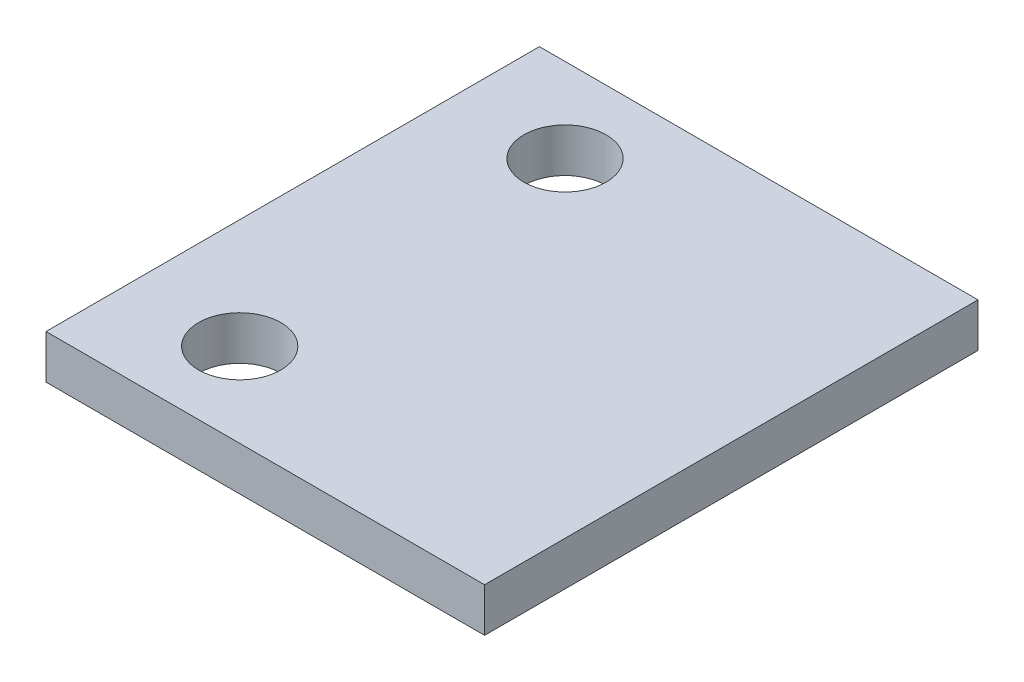
SolidWorks part; units mm, degrees
ref_plane "Front Plane" through (0, 0, 0) normal (0, 0, 1) x (1, 0, 0)
ref_plane "Top Plane" through (0, 0, 0) normal (0, 1, 0) x (1, 0, 0)
ref_plane "Right Plane" through (0, 0, 0) normal (1, 0, 0) x (0, 0, -1)
sketch "Sketch1" plane through (0, 0, 0) normal (0, 1, 0) x (1, 0, 0)
  line L1 (-25.4, 28.575) -> (25.4, 28.575)
  line L2 (-25.4, 28.575) -> (-25.4, -28.575)
  line L3 (-25.4, -28.575) -> (25.4, -28.575)
  line L4 (25.4, 28.575) -> (25.4, -28.575)
  line L5 (-25.4, 28.575) -> (25.4, -28.575) construction
  line L6 (-25.4, -28.575) -> (25.4, 28.575) construction
  point P4 (0, 0)
  dimension "D1" = 50.8
  dimension "D2" = 57.15
extrude "Boss-Extrude1" add sketch "Sketch1" along normal blind 5.08
sketch "Sketch2" plane through (0, 5.08, 0) normal (0, 1, 0) x (1, 0, 0)
  line L0 (-12.7, -18.8377) -> (-12.7, 18.8377) construction
  line L3 (-25.4, 18.8377) -> (25.4, 18.8377) construction
  line L4 (-25.4, 28.575) -> (-25.4, -28.575) construction
  line L5 (25.4, -28.575) -> (25.4, 28.575) construction
  line L6 (-25.4, -18.8377) -> (25.4, -18.8377) construction
  line L7 (-12.7, 0) -> (25.4, 0) construction
  circle A0 centre (-12.7, 18.8377) radius 4.7625
  circle A1 centre (-12.7, -18.8377) radius 4.7625
  dimension "D2" = 9.525
  dimension "D1" = 9.525
  dimension "D3" = 37.6753
  dimension "D4" = 38.1
extrude "Cut-Extrude1" cut sketch "Sketch2" against normal blind 5.08
